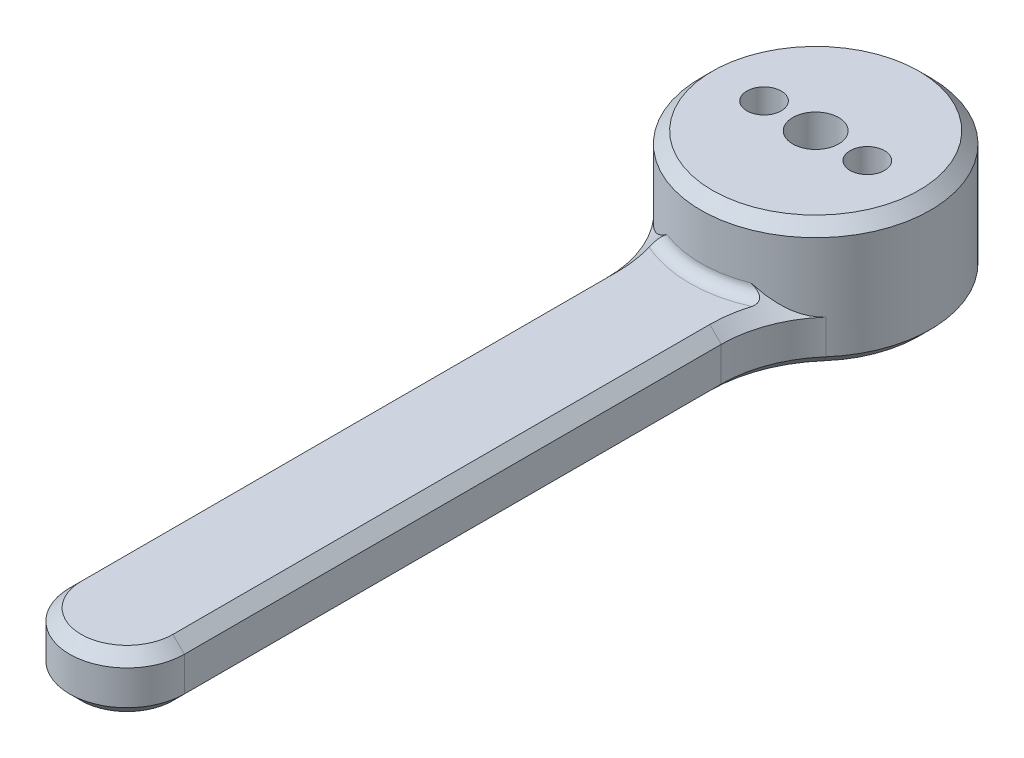
SolidWorks part; units mm, degrees
ref_plane "Front Plane" through (0, 0, 0) normal (0, 0, 1) x (1, 0, 0)
ref_plane "Top Plane" through (0, 0, 0) normal (0, 1, 0) x (1, 0, 0)
ref_plane "Right Plane" through (0, 0, 0) normal (1, 0, 0) x (0, 0, -1)
sketch "Sketch1" plane through (0, 0, 0) normal (0, 1, 0) x (1, 0, 0)
  line L0 (0, 0) -> (0, -120) construction
  line L1 (10, -26.4575) -> (10, -120)
  line L2 (-10, -26.4575) -> (-10, -120)
  arc A0 (15, -13.2288) -> (-15, -13.2288) centre (0, 0) ccw
  arc A2 (-10, -120) -> (10, -120) centre (0, -120) ccw
  arc A3 (10, -26.4575) -> (15, -13.2288) centre (30, -26.4575) cw
  arc A4 (-10, -26.4575) -> (-15, -13.2288) centre (-30, -26.4575) ccw
  point P5 (0, -60)
  dimension "D1" = 40
  dimension "D5" = 20
  dimension "D2" = 20
  dimension "D3" = 120
  dimension "D4" = 60
extrude "Boss-Extrude1" add sketch "Sketch1" along normal blind 22
sketch "Sketch2" plane through (0, 22, 0) normal (0, 1, 0) x (1, 0, 0)
  line L0 (-20, 0) -> (-32.7413, 0)
  line L1 (-32.7413, 0) -> (-32.7413, -139.1492)
  line L2 (-32.7413, -139.1492) -> (49.3116, -139.1492)
  line L3 (49.3116, -139.1492) -> (49.3116, 0)
  line L4 (49.3116, 0) -> (20, 0)
  arc A0 (-20, 0) -> (20, 0) centre (0, 0) ccw
extrude "Cut-Extrude1" cut sketch "Sketch2" against normal blind 12
sketch "Sketch4" plane through (0, 22, 0) normal (0, 1, 0) x (1, 0, 0)
  circle A0 centre (0, 0) radius 4
  dimension "D1" = 8
extrude "Cut-Extrude2" cut sketch "Sketch4" against normal through all
sketch "Sketch5" plane through (0, 22, 0) normal (0, 1, 0) x (1, 0, 0)
  circle A0 centre (-9, 0) radius 3
  dimension "D2" = 6
  dimension "D1" = 9
extrude "Cut-Extrude3" cut sketch "Sketch5" against normal blind 20
mirror "Mirror1" about plane through (0, 0, 0) normal (1, 0, 0) of "Cut-Extrude3"
chamfer "Chamfer1" distance 2 angle 45 12 edges at (11.2917, 10, 19.3864) (10, 10, 73.2288) (-11.2917, 10, 19.3864) (0, 10, 130) (-10, 10, 73.2288) (11.2917, 0, 19.3864) (0, 0, -20) (10, 0, 73.2288) (-11.2917, 0, 19.3864) (0, 0, 130) (-10, 0, 73.2288) (0, 22, 20)
fillet "Fillet1" radius 2 1 edges at (0, 10, 20)
